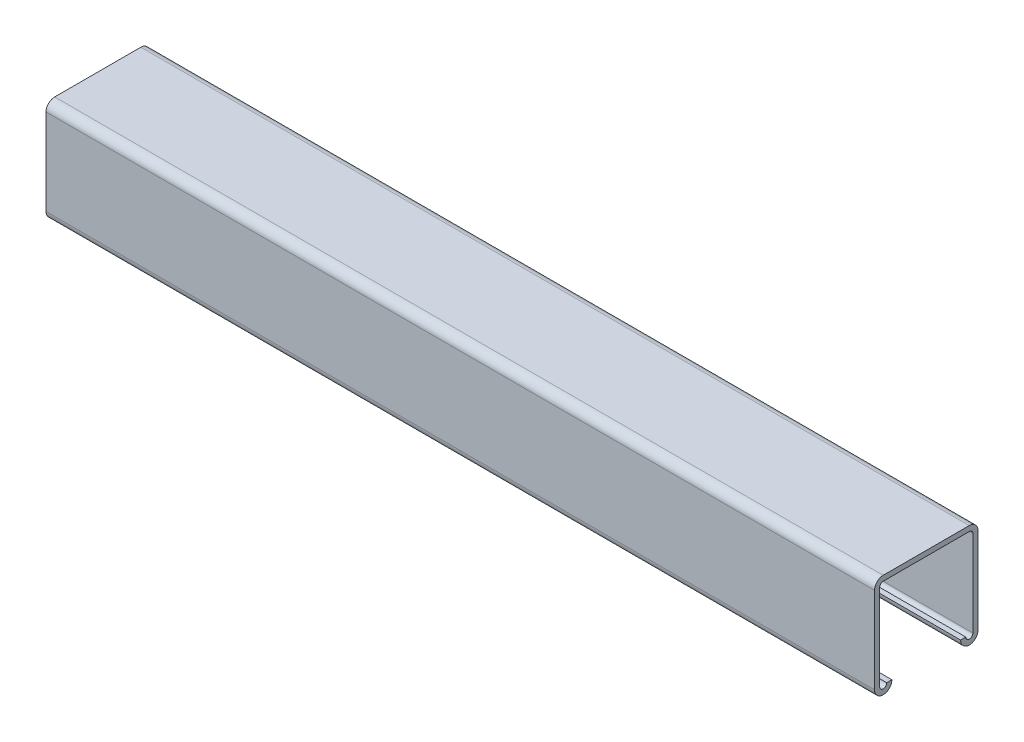
SolidWorks part; units mm, degrees
ref_plane "Top" through (0, 0, 0) normal (0, 0, 1) x (1, 0, 0)
ref_plane "Front" through (0, 0, 0) normal (0, 1, 0) x (1, 0, 0)
ref_plane "Right" through (0, 0, 0) normal (1, 0, 0) x (0, 0, -1)
ref_axis "CentralAxis" through (-50, 0, 0) along (1, 0, 0)
sketch "Sketch1" plane through (0, 39.2434, 0) normal (1, 0, 0) x (0, 0, 1)
  line L0 (0, 39.2434) -> (0, 95.6362) construction
  line L1 (-15.85, 39.2434) -> (15.85, 39.2434)
  line L2 (19.05, 42.4434) -> (19.05, 74.1434)
  line L3 (-19.05, 42.4434) -> (-19.05, 74.1434)
  arc A0 (15.85, 39.2434) -> (19.05, 42.4434) centre (15.85, 42.4434) ccw
  arc A1 (-15.85, 39.2434) -> (-19.05, 42.4434) centre (-15.85, 42.4434) cw
  arc A2 (19.05, 74.1434) -> (12.65, 74.1434) centre (15.85, 74.1434) ccw
  arc A3 (-19.05, 74.1434) -> (-12.65, 74.1434) centre (-15.85, 74.1434) cw
  dimension "D1" = 3.2
  dimension "D4" = 6.4
  dimension "square" = 38.1
  dimension "ChDepth" = 38.1
extrude "Channel" add sketch "Sketch1" along normal blind 305 thin thin type one direction wall 1.9
sketch "Sketch2" plane through (0, 0, 0) normal (0, 1, 0) x (-1, 0, 0)
  line L0 (-305, 15.85) -> (-305, -15.85) construction
  line L1 (50, 0) -> (-50, 0) construction
  circle A0 centre (-286, 0) radius 9.5
  dimension "TopHoleDia" = 19
  dimension "D2" = 19
extrude "TopHole" [suppressed] cut sketch "Sketch2" against normal through all
sketch "Sketch3" plane through (568.1866, -17.9535, 19.05) normal (0, 0, 1) x (1, 0, 0)
  line L3 (-263.1866, -16.9465) -> (-263.1866, 14.7535) construction
  line L4 (-568.1866, -20.1465) -> (-263.1866, -20.1465) construction
  circle A0 centre (-282.1866, -1.1465) radius 9.5
  dimension "SideHoleDia" = 19
  dimension "D2" = 19
  dimension "D3" = 19
extrude "SideHole" [suppressed] cut sketch "Sketch3" against normal through all
sketch "Sketch4" plane through (0, 0, 0) normal (0, 1, 0) x (-1, 0, 0)
  line L0 (-305, 0) -> (-214.3896, 0) construction
  line L1 (-305, 15.85) -> (-305, -15.85) construction
  line L2 (-240.25, -5.15) -> (-287.15, -5.15)
  line L3 (-240.25, 5.15) -> (-287.15, 5.15)
  arc A0 (-287.15, 5.15) -> (-287.15, -5.15) centre (-287.15, 0) ccw
  arc A1 (-240.25, 5.15) -> (-240.25, -5.15) centre (-240.25, 0) cw
  dimension "D3" = 57.2
  dimension "D1" = 12.7
  dimension "D2" = 10.3
extrude "Slot" [suppressed] cut sketch "Sketch4" against normal through all
pattern_linear "TopHolePatt" [suppressed] count 7 spacing 44.5 along (-1, 0, 0)
pattern_linear "SideHolePatt" [suppressed] count 7 spacing 44.5 along (-1, 0, 0)
pattern_linear "LPattern3" [suppressed] count 3 spacing 101.6 along (-1, 0, 0)
